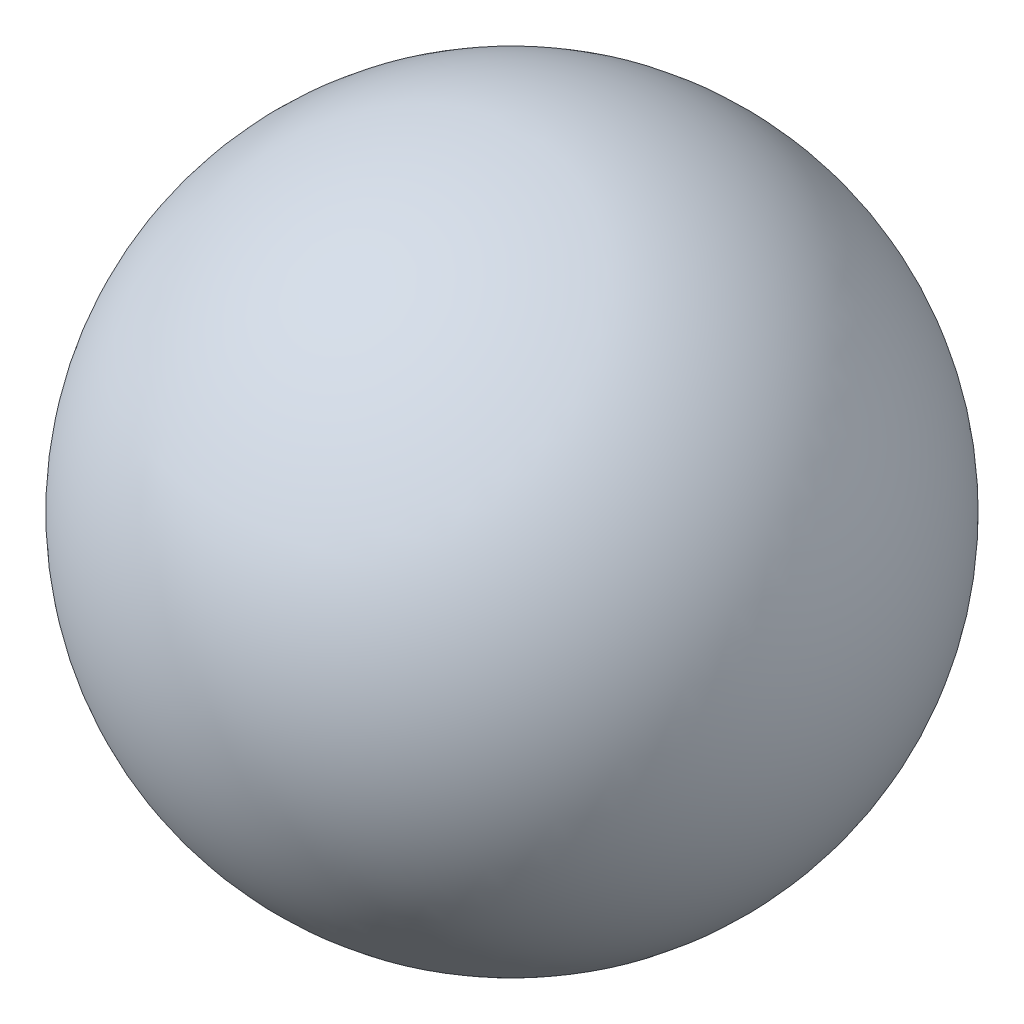
SolidWorks part; units mm, degrees
ref_plane "Front Plane" through (0, 0, 0) normal (0, 0, 1) x (1, 0, 0)
ref_plane "Top Plane" through (0, 0, 0) normal (0, 1, 0) x (1, 0, 0)
ref_plane "Right Plane" through (0, 0, 0) normal (1, 0, 0) x (0, 0, -1)
sketch "Sketch1" plane through (0, 0, 0) normal (0, 0, 1) x (1, 0, 0)
  line L1 (0, -127) -> (0, 127)
  circle A0 centre (0, 0) radius 127
  dimension "D1" = 254
revolve "Revolve1" add sketch "Sketch1" angle 360 about L1 region at (-53.9005, 0, 0)
